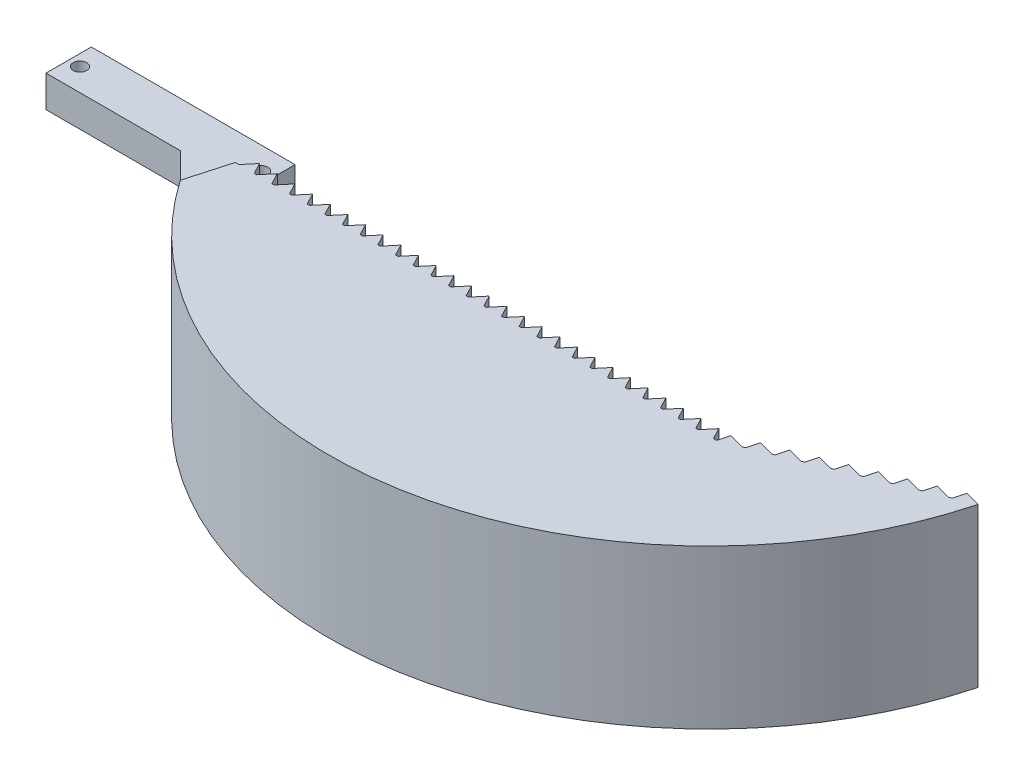
SolidWorks part; units mm, degrees
ref_plane "Front Plane" through (0, 0, 0) normal (0, 0, 1) x (1, 0, 0)
ref_plane "Top Plane" through (0, 0, 0) normal (0, 1, 0) x (1, 0, 0)
ref_plane "Right Plane" through (0, 0, 0) normal (1, 0, 0) x (0, 0, -1)
sketch "Sketch1" plane through (0, 0, 0) normal (0, 1, 0) x (1, 0, 0)
  line L1 (-22.5, -5) -> (22.5, -5)
  line L2 (-22.5, -5) -> (-22.5, 5)
  line L3 (-22.5, 5) -> (22.5, 5)
  line L4 (22.5, -5) -> (22.5, 5)
  line L5 (-22.5, -5) -> (22.5, 5) construction
  line L6 (-22.5, 5) -> (22.5, -5) construction
  point P0 (0, 0)
  dimension "D1" = 45
  dimension "D2" = 10
extrude "Boss-Extrude1" add sketch "Sketch1" along normal blind 7
sketch "Sketch2" plane through (0, 7, 0) normal (0, 1, 0) x (1, 0, 0)
  circle A0 centre (-20, 0) radius 1.5
  circle A1 centre (20, 0) radius 1.5
  dimension "D1" = 3
  dimension "D2" = 40
  dimension "D3" = 20
extrude "Cut-Extrude1" cut sketch "Sketch2" against normal blind 15
sketch "Sketch5" plane through (0, 7, 0) normal (0, 1, 0) x (1, 0, 0)
  line L0 (19.3, -5) -> (32.9888, -18.6889)
  line L1 (-22.5, -5) -> (22.5, -5) construction
  line L2 (32.9888, -18.6889) -> (139.4298, -18.6889)
  line L3 (180.396, -2.0927) -> (177.0163, -1.1879)
  line L4 (177.0163, -1.1879) -> (176.3334, -3.7385)
  line L5 (30.3175, -28.163) -> (7.1545, -5)
  line L6 (180.396, -2.0927) -> (139.4298, -18.6889)
  line L7 (175.7618, -3.9701) -> (172.3821, -3.0653)
  line L8 (172.3821, -3.0653) -> (171.6993, -5.6159)
  line L9 (171.1277, -5.8475) -> (167.748, -4.9426)
  line L10 (167.748, -4.9426) -> (167.0651, -7.4933)
  line L11 (166.4935, -7.7249) -> (163.1138, -6.82)
  line L12 (163.1138, -6.82) -> (162.4309, -9.3707)
  line L13 (161.8593, -9.6022) -> (158.4796, -8.6974)
  line L14 (158.4796, -8.6974) -> (157.7968, -11.2481)
  line L15 (157.2252, -11.4796) -> (153.8455, -10.5748)
  line L16 (153.8455, -10.5748) -> (153.1626, -13.1254)
  line L17 (152.591, -13.357) -> (149.2113, -12.4522)
  line L18 (149.2113, -12.4522) -> (148.5285, -15.0028)
  line L19 (147.9569, -15.2344) -> (144.5772, -14.3296)
  line L20 (144.5772, -14.3296) -> (143.8943, -16.8802)
  line L21 (143.3227, -17.1118) -> (139.943, -16.207)
  line L22 (139.943, -16.207) -> (139.2602, -18.7576)
  line L23 (138.5692, -18.6889) -> (137.2777, -16.207)
  line L24 (137.2777, -16.207) -> (135.1945, -18.6889)
  line L25 (134.6692, -18.6889) -> (133.3777, -16.207)
  line L26 (133.3777, -16.207) -> (131.2945, -18.6889)
  line L27 (130.7692, -18.6889) -> (129.4777, -16.207)
  line L28 (129.4777, -16.207) -> (127.3945, -18.6889)
  line L29 (126.8692, -18.6889) -> (125.5777, -16.207)
  line L30 (125.5777, -16.207) -> (123.4945, -18.6889)
  line L31 (122.9692, -18.6889) -> (121.6777, -16.207)
  line L32 (121.6777, -16.207) -> (119.5945, -18.6889)
  line L33 (119.0692, -18.6889) -> (117.7777, -16.207)
  line L34 (117.7777, -16.207) -> (115.6945, -18.6889)
  line L35 (115.1692, -18.6889) -> (113.8777, -16.207)
  line L36 (113.8777, -16.207) -> (111.7945, -18.6889)
  line L37 (111.2692, -18.6889) -> (109.9777, -16.207)
  line L38 (109.9777, -16.207) -> (107.8945, -18.6889)
  line L39 (107.3692, -18.6889) -> (106.0777, -16.207)
  line L40 (106.0777, -16.207) -> (103.9945, -18.6889)
  line L41 (103.4692, -18.6889) -> (102.1777, -16.207)
  line L42 (102.1777, -16.207) -> (100.0945, -18.6889)
  line L43 (99.5692, -18.6889) -> (98.2777, -16.207)
  line L44 (98.2777, -16.207) -> (96.1945, -18.6889)
  line L45 (95.6692, -18.6889) -> (94.3777, -16.207)
  line L46 (94.3777, -16.207) -> (92.2945, -18.6889)
  line L47 (91.7692, -18.6889) -> (90.4777, -16.207)
  line L48 (90.4777, -16.207) -> (88.3945, -18.6889)
  line L49 (87.8692, -18.6889) -> (86.5777, -16.207)
  line L50 (86.5777, -16.207) -> (84.4945, -18.6889)
  line L51 (83.9692, -18.6889) -> (82.6777, -16.207)
  line L52 (82.6777, -16.207) -> (80.5945, -18.6889)
  line L53 (80.0692, -18.6889) -> (78.7777, -16.207)
  line L54 (78.7777, -16.207) -> (76.6945, -18.6889)
  line L55 (76.1692, -18.6889) -> (74.8777, -16.207)
  line L56 (74.8777, -16.207) -> (72.7945, -18.6889)
  line L57 (72.2692, -18.6889) -> (70.9777, -16.207)
  line L58 (70.9777, -16.207) -> (68.8945, -18.6889)
  line L59 (68.3692, -18.6889) -> (67.0777, -16.207)
  line L60 (67.0777, -16.207) -> (64.9945, -18.6889)
  line L61 (64.4692, -18.6889) -> (63.1777, -16.207)
  line L62 (63.1777, -16.207) -> (61.0945, -18.6889)
  line L63 (60.5692, -18.6889) -> (59.2777, -16.207)
  line L64 (59.2777, -16.207) -> (57.1945, -18.6889)
  line L65 (56.6692, -18.6889) -> (55.3777, -16.207)
  line L66 (55.3777, -16.207) -> (53.2945, -18.6889)
  line L67 (52.7692, -18.6889) -> (51.4777, -16.207)
  line L68 (51.4777, -16.207) -> (49.3945, -18.6889)
  line L69 (48.8692, -18.6889) -> (47.5777, -16.207)
  line L70 (47.5777, -16.207) -> (45.4945, -18.6889)
  line L71 (44.9692, -18.6889) -> (43.6777, -16.207)
  line L72 (43.6777, -16.207) -> (41.5945, -18.6889)
  line L73 (41.0692, -18.6889) -> (39.7777, -16.207)
  line L74 (39.7777, -16.207) -> (37.6945, -18.6889)
  line L75 (37.1692, -18.6889) -> (35.8777, -16.207)
  line L76 (35.8777, -16.207) -> (33.7945, -18.6889)
  line L77 (19.3, -5) -> (7.1545, -5)
  line L78 (19.3, -5) -> (22.5, -5)
  line L79 (22.5, -5) -> (22.5, 5) construction
  line L80 (32.9888, -18.6889) -> (30.3175, -28.163)
  arc A0 (180.396, -2.0927) -> (30.3175, -28.163) centre (99.322, 19.6124) cw
  dimension "D1" = 9
  dimension "D2" = 27
extrude "Boss-Extrude2" add sketch "Sketch5" against normal blind 7 contours L77 L5 L80 L0
extrude "Boss-Extrude3" add sketch "Sketch5<6>" against normal mid plane 35 contours A0 L6 L2 | L75 L76 L2 | L73 L74 L2 | L71 L72 L2 | L69 L70 L2 | L67 L68 L2 | L63 L64 L2 | L65 L66 L2 | L61 L62 L2 | L59 L60 L2 | L57 L58 L2 | L55 L56 L2 | L53 L54 L2 | L51 L52 L2 | L49 L50 L2 | L47 L48 L2 | L45 L46 L2 | L43 L44 L2 | L41 L42 L2 | L39 L40 L2 | L37 L38 L2 | L35 L36 L2 | L33 L34 L2 | L31 L32 L2 | L29 L30 L2 | L27 L28 L2 | L25 L26 L2 | L23 L24 L2 | L21 L22 L2 L6 | L19 L20 L6 | L17 L18 L6 | L15 L16 L6 | L13 L14 L6 | L11 L12 L6 | L9 L10 L6 | L7 L8 L6 | L6 L3 L4 region at (103.6267, 7, 36.1789) region at (35.6138, 7, 17.8616) region at (177.9152, 7, 2.3397) region at (39.5138, 7, 17.8616) region at (173.2811, 7, 4.2171) region at (43.4138, 7, 17.8616) region at (168.6469, 7, 6.0945) region at (47.3138, 7, 17.8616) region at (164.0127, 7, 7.9719) region at (51.2138, 7, 17.8616) region at (159.3786, 7, 9.8492) region at (55.1138, 7, 17.8616) region at (154.7444, 7, 11.7266) region at (59.0138, 7, 17.8616) region at (150.1103, 7, 13.604) region at (62.9138, 7, 17.8616) region at (145.4761, 7, 15.4814) region at (66.8138, 7, 17.8616) region at (140.8437, 7, 17.3573) region at (70.7138, 7, 17.8616) region at (74.6138, 7, 17.8616) region at (137.0138, 7, 17.8616) region at (78.5138, 7, 17.8616) region at (133.1138, 7, 17.8616) region at (82.4138, 7, 17.8616) region at (129.2138, 7, 17.8616) region at (86.3138, 7, 17.8616) region at (125.3138, 7, 17.8616) region at (90.2138, 7, 17.8616) region at (121.4138, 7, 17.8616) region at (94.1138, 7, 17.8616) region at (117.5138, 7, 17.8616) region at (98.0138, 7, 17.8616) region at (113.6138, 7, 17.8616) region at (101.9138, 7, 17.8616) region at (109.7138, 7, 17.8616) region at (105.8138, 7, 17.8616)
sketch "Sketch5<6>" plane through (0, 7, 0) normal (0, 1, 0) x (1, 0, 0) same geometry as "Sketch5"
